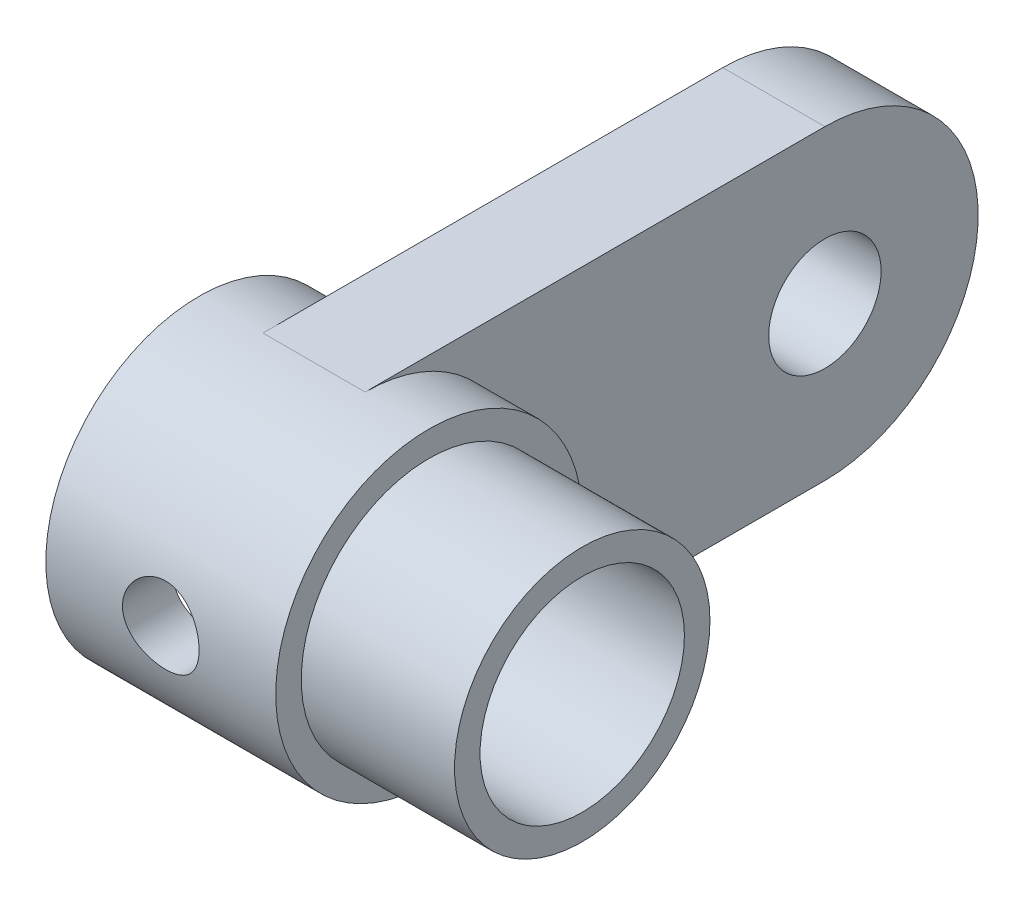
SolidWorks part; units mm, degrees
ref_plane "前视基准面" through (0, 0, 0) normal (0, 0, 1) x (1, 0, 0)
ref_plane "上视基准面" through (0, 0, 0) normal (0, 1, 0) x (1, 0, 0)
ref_plane "右视基准面" through (0, 0, 0) normal (1, 0, 0) x (0, 0, -1)
sketch "草图5" plane through (0, 0, 0) normal (1, 0, 0) x (0, 0, -1)
  line L2 (0, -6) -> (18, -6)
  line L4 (18, 6) -> (0, 6)
  arc A0 (18, -6) -> (18, 6) centre (18, 0) ccw
  arc A2 (0, 6) -> (0, -6) centre (0, 0) ccw
  dimension "D1" = 12
  dimension "D2" = 18
sketch "草图7" plane through (0, 0, 0) normal (1, 0, 0) x (0, 0, -1)
  arc A1 (3.4641, 2) -> (3.4641, -2) centre (0, 0) ccw
  arc A2 (3.4641, 2) -> (3.4641, -2) centre (0, 0) cw
  point P11 (4, 0)
extrude "凸台-拉伸2" add sketch "草图5" along normal blind 4.5 and the other way blind 4.5 contours L4 A2 L2 A0
extrude "切除-拉伸1" cut sketch "草图7" against normal blind 6 and the other way blind 7 contours A1 A2
sketch "草图10" plane through (0, 0, 0) normal (1, 0, 0) x (0, 0, -1)
  circle A2 centre (18, 0) radius 2.2
extrude "切除-拉伸2" cut sketch "草图10" against normal blind 6 and the other way blind 6
ref_plane "基准面2" through (-4.5, 0, 0) normal (-1, 0, 0) x (0, 0, 1)
sketch "草图11" plane through (-4.5, 0, 0) normal (-1, 0, 0) x (0, 0, 1)
  line L4 (-18, 6) -> (0, 6)
  line L8 (0, -6) -> (-18, -6)
  arc A0 (0, 6) -> (0, -6) centre (0, 0) ccw
  arc A1 (-18, 6) -> (-18, -6) centre (-18, 0) ccw
extrude "切除-拉伸3" cut sketch "草图11" against normal blind 2.5
ref_plane "基准面3" through (0, 0, 0) normal (1, 0, 0) x (0, 0, -1)
ref_plane "基准面4" through (4.5, 0, 0) normal (1, 0, 0) x (0, 0, -1)
mirror "镜向2" about plane through (0, 0, 0) normal (1, 0, 0) of "切除-拉伸3"
sketch "草图13" plane through (-2, 0, 0) normal (-1, 0, 0) x (0, 0, 1)
  circle A0 centre (-18, 0) radius 2.2
  circle A1 centre (-18, 0) radius 3.5
  dimension "D1" = 7
  dimension "D2" = 4.4
extrude "凸台-拉伸3" add sketch "草图13" along normal blind 2
chamfer "倒角3" distance 0.5 angle 45 1 edges at (-4, 0, -14.5)
sketch "草图18" plane through (4.5, 0, 0) normal (1, 0, 0) x (0, 0, -1)
  circle A0 centre (0, 0) radius 5
  dimension "D1" = 10
extrude "凸台-拉伸5" add sketch "草图18" along normal blind 6
sketch "草图19" plane through (10.5, 0, 0) normal (1, 0, 0) x (0, 0, -1)
  circle A0 centre (0, 0) radius 4
extrude "切除-拉伸5" cut sketch "草图19" against normal blind 16
chamfer "倒角4" distance 1 angle 45 1 edges at (-4.5, 0, -4)
ref_plane "基准面9" through (0, 6, 0) normal (0, 1, 0) x (1, 0, 0)
ref_plane "基准面11" through (0, 0, 6) normal (0, 0, 1) x (1, 0, 0)
sketch "草图22" plane through (0, 0, 6) normal (0, 0, 1) x (1, 0, 0)
  circle A0 centre (0, 0) radius 1.5
  dimension "D1" = 3
extrude "切除-拉伸6" cut sketch "草图22" against normal blind 10
